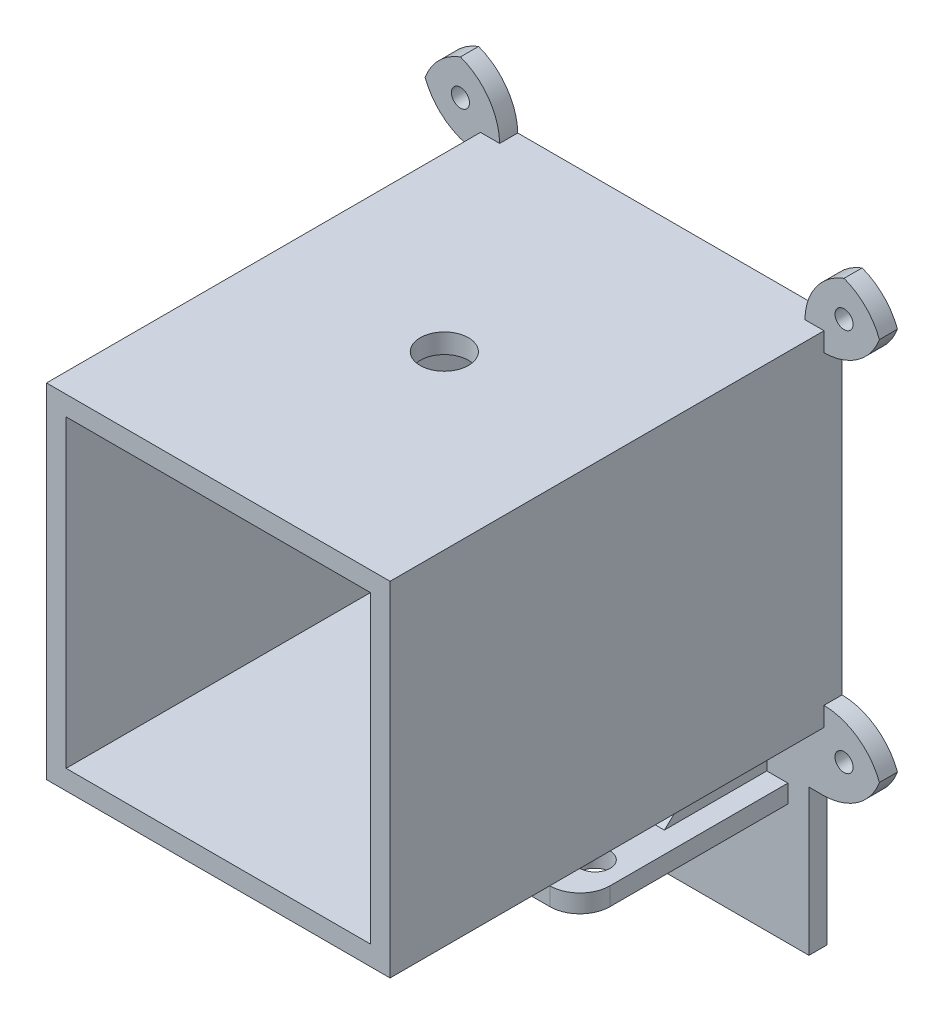
SolidWorks part; units mm, degrees
material "ABS"
ref_plane "Plan de face" through (0, 0, 0) normal (0, 0, 1) x (1, 0, 0)
ref_plane "Plan de dessus" through (0, 0, 0) normal (0, 1, 0) x (1, 0, 0)
ref_plane "Plan de droite" through (0, 0, 0) normal (1, 0, 0) x (0, 0, -1)
sketch "Esquisse1" plane through (0, 0, 0) normal (0, 0, 1) x (1, 0, 0)
  line L1 (25.25, -25.25) -> (-25.25, -25.25)
  line L2 (25.25, -25.25) -> (25.25, 25.25)
  line L3 (25.25, 25.25) -> (-25.25, 25.25)
  line L4 (-25.25, -25.25) -> (-25.25, 25.25)
  line L5 (25.25, -25.25) -> (-25.25, 25.25) construction
  line L6 (25.25, 25.25) -> (-25.25, -25.25) construction
  line L7 (28.5, -28.5) -> (-28.5, -28.5)
  line L8 (28.5, -28.5) -> (28.5, 28.5)
  line L9 (28.5, 28.5) -> (-28.5, 28.5)
  line L10 (-28.5, -28.5) -> (-28.5, 28.5)
  line L11 (28.5, -28.5) -> (-28.5, 28.5) construction
  line L12 (28.5, 28.5) -> (-28.5, -28.5) construction
  point P0 (0, 0)
  point P6 (0, 0)
  dimension "D1" = 50.5
  dimension "D2" = 57
  dimension "D3" = 57
extrude "Boss.-Extru.1" add sketch "Esquisse1" along normal blind 75
sketch "Esquisse2" plane through (0, -28.5, 0) normal (0, -1, 0) x (1, 0, 0)
  line L0 (-28.5, 75) -> (28.5, 0) construction
  circle A0 centre (0, 37.5) radius 4
  dimension "D1" = 8
extrude "Enlèv. mat.-Extru.1" cut sketch "Esquisse2" against normal through all both and the other way through all
sketch "Esquisse3" plane through (0, 0, 0) normal (0, 0, -1) x (-1, 0, 0)
  line L0 (0, 0) -> (0, -70.927) construction
  line L1 (28.5, -28.5) -> (-28.5, -28.5) construction
  line L2 (-26, -62.5) -> (26, -62.5)
  line L3 (-26, -62.5) -> (-26, -28.5)
  line L4 (-26, -28.5) -> (26, -28.5)
  line L5 (26, -62.5) -> (26, -28.5)
  line L6 (-26, -62.5) -> (26, -28.5) construction
  line L7 (-26, -28.5) -> (26, -62.5) construction
  point P3 (0, -45.5)
  dimension "D1" = 52
  dimension "D2" = 34
extrude "Boss.-Extru.2" add sketch "Esquisse3" against normal blind 3
sketch "Esquisse4" plane through (0, -62.5, 0) normal (0, -1, 0) x (1, 0, 0)
  line L0 (0, 0) -> (0, 33.5) construction
  line L1 (26, 0) -> (-26, 0) construction
  line L2 (0, 37.5) -> (-17.5, 37.5) construction
  line L3 (-22.5, 3) -> (-22.5, 37.5)
  line L4 (-26, 3) -> (26, 3) construction
  line L5 (22.5, 3) -> (22.5, 37.5)
  line L6 (-22.5, 3) -> (22.5, 3)
  line L7 (26, 3) -> (-26, 3) construction
  line L8 (-5, 37.5) -> (-22.5, 37.5)
  line L9 (5, 37.5) -> (22.5, 37.5)
  circle A0 centre (0, 37.5) radius 4 construction
  arc A1 (-5, 37.5) -> (5, 37.5) centre (0, 37.5) ccw
  circle A2 centre (-17.5, 30) radius 2.5
  circle A4 centre (17.5, 30) radius 2.5
  dimension "D1" = 10
  dimension "D2" = 5
  dimension "D3" = 7.5
  dimension "D4" = 17.5
  dimension "D5" = 45
extrude "Boss.-Extru.3" add sketch "Esquisse4" along normal blind 3 from offset 23 offset against normal yes
fillet "Congé1" radius 5 2 edges at (-22.5, -41, 37.5) (22.5, -41, 37.5)
sketch "Esquisse8" plane through (-22.5, 0, 0) normal (-1, 0, 0) x (0, 0, 1)
  line L0 (3, -28.5) -> (8, -28.5)
  line L1 (75, -28.5) -> (0, -28.5) construction
  line L2 (8, -28.5) -> (20, -39.5)
  line L3 (32.5, -39.5) -> (3, -39.5) construction
  line L4 (20, -39.5) -> (3, -39.5)
  line L5 (3, -39.5) -> (3, -28.5)
  dimension "D1" = 5
  dimension "D2" = 17
extrude "Boss.-Extru.4" add sketch "Esquisse8" along normal blind 3 from offset 6.5 offset against normal yes
mirror "Symétrie1" about plane through (0, 0, 0) normal (1, 0, 0) of "Boss.-Extru.4"
sketch "Esquisse9" plane through (0, 0, 0) normal (0, 0, -1) x (-1, 0, 0)
  line L0 (-31.8198, -31.8198) -> (31.8198, 31.8198) construction
  line L1 (-31.8198, 31.8198) -> (31.8198, -31.8198) construction
  line L3 (-25.3198, 25.3198) -> (-38.3198, 25.3198)
  line L4 (-25.3198, 25.3198) -> (-25.3198, 38.3198)
  line L5 (-25.3198, 38.3198) -> (-38.3198, 38.3198)
  line L6 (-38.3198, 25.3198) -> (-38.3198, 38.3198)
  line L7 (-25.3198, 25.3198) -> (-38.3198, 38.3198) construction
  line L8 (-25.3198, 38.3198) -> (-38.3198, 25.3198) construction
  line L9 (38.3198, 25.3198) -> (25.3198, 25.3198)
  line L10 (38.3198, 25.3198) -> (38.3198, 38.3198)
  line L11 (38.3198, 38.3198) -> (25.3198, 38.3198)
  line L12 (25.3198, 25.3198) -> (25.3198, 38.3198)
  line L13 (38.3198, 25.3198) -> (25.3198, 38.3198) construction
  line L14 (38.3198, 38.3198) -> (25.3198, 25.3198) construction
  line L15 (38.3198, -38.3198) -> (25.3198, -38.3198)
  line L16 (38.3198, -38.3198) -> (38.3198, -25.3198)
  line L17 (38.3198, -25.3198) -> (25.3198, -25.3198)
  line L18 (25.3198, -38.3198) -> (25.3198, -25.3198)
  line L19 (38.3198, -38.3198) -> (25.3198, -25.3198) construction
  line L20 (38.3198, -25.3198) -> (25.3198, -38.3198) construction
  line L21 (-38.3198, -38.3198) -> (-25.3198, -38.3198)
  line L22 (-38.3198, -38.3198) -> (-38.3198, -25.3198)
  line L23 (-38.3198, -25.3198) -> (-25.3198, -25.3198)
  line L24 (-25.3198, -38.3198) -> (-25.3198, -25.3198)
  line L25 (-38.3198, -38.3198) -> (-25.3198, -25.3198) construction
  line L26 (-38.3198, -25.3198) -> (-25.3198, -38.3198) construction
  circle A0 centre (0, 0) radius 45 construction
  circle A1 centre (-31.8198, 31.8198) radius 1.5
  circle A2 centre (31.8198, 31.8198) radius 1.5
  circle A3 centre (31.8198, -31.8198) radius 1.5
  circle A4 centre (-31.8198, -31.8198) radius 1.5
  point P5 (0, 0)
  dimension "D2" = 3
  dimension "D3" = 3
  dimension "D4" = 3
  dimension "D5" = 3
  dimension "D1" = 90
  dimension "D6" = 90
  dimension "D7" = 13
extrude "Boss.-Extru.5" add sketch "Esquisse9" against normal blind 3
fillet "Congé2" radius 10 10 edges at (-38.3198, -38.3198, 1.5) (-38.3198, -25.3198, 1.5) (38.3198, -38.3198, 1.5) (38.3198, -25.3198, 1.5) (38.3198, 25.3198, 1.5) (38.3198, 38.3198, 1.5) (25.3198, 38.3198, 1.5) (-25.3198, 38.3198, 1.5) (-38.3198, 38.3198, 1.5) (-38.3198, 25.3198, 1.5)
